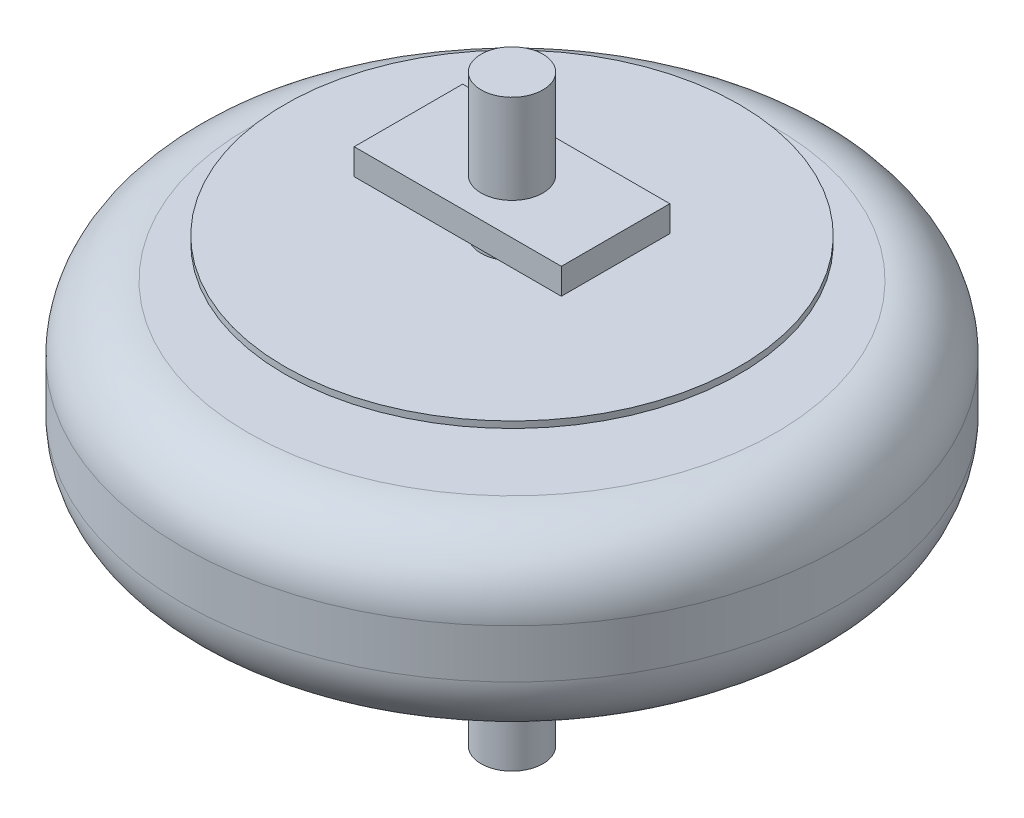
SolidWorks part; units mm, degrees
ref_plane "Front Plane" through (0, 0, 0) normal (0, 0, 1) x (1, 0, 0)
ref_plane "Top Plane" through (0, 0, 0) normal (0, 1, 0) x (1, 0, 0)
ref_plane "Right Plane" through (0, 0, 0) normal (1, 0, 0) x (0, 0, -1)
sketch "Sketch1" plane through (0, 0, 0) normal (0, 1, 0) x (1, 0, 0)
  circle A0 centre (0, 0) radius 101.6
  dimension "D1" = 203.2
extrude "Boss-Extrude1" add sketch "Sketch1" along normal mid plane 55.626
sketch "Sketch2" plane through (0, 27.813, 0) normal (0, 1, 0) x (1, 0, 0)
  circle A0 centre (0, 0) radius 9.525
  dimension "D1" = 19.05
extrude "Boss-Extrude2" add sketch "Sketch2" along normal blind 55.626 and the other way blind 124.206
fillet "Fillet1" radius 20.32 2 edges at (0, -27.813, 101.6) (0, 27.813, 101.6)
ref_plane "Plane1" through (0, 37.813, 0) normal (0, 1, 0) x (1, 0, 0)
sketch "Sketch4" plane through (0, 37.813, 0) normal (0, 1, 0) x (1, 0, 0)
  circle A0 centre (0, 0) radius 70
  dimension "D1" = 140
extrude "Boss-Extrude4" add sketch "Sketch4" along normal blind 2
ref_plane "Plane2" through (0, 55.913, 0) normal (0, 1, 0) x (1, 0, 0)
sketch "Sketch5" plane through (0, 55.913, 0) normal (0, 1, 0) x (1, 0, 0)
  line L1 (-31.9129, -16.7066) -> (31.9129, -16.7066)
  line L2 (-31.9129, -16.7066) -> (-31.9129, 16.7066)
  line L3 (-31.9129, 16.7066) -> (31.9129, 16.7066)
  line L4 (31.9129, -16.7066) -> (31.9129, 16.7066)
  line L5 (-31.9129, -16.7066) -> (31.9129, 16.7066) construction
  line L6 (-31.9129, 16.7066) -> (31.9129, -16.7066) construction
  point P0 (0, 0)
extrude "Boss-Extrude5" add sketch "Sketch5" against normal blind 8
